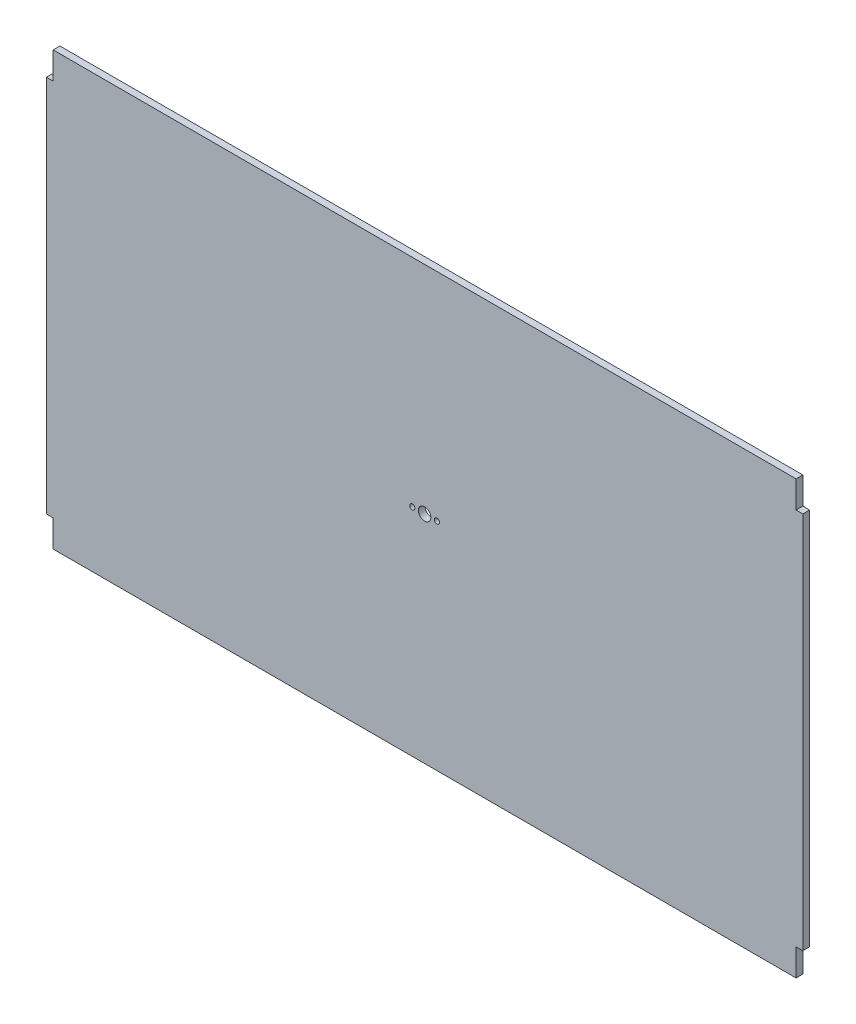
SolidWorks part; units mm, degrees
ref_plane "Front Plane" through (0, 0, 0) normal (0, 0, 1) x (1, 0, 0)
ref_plane "Top Plane" through (0, 0, 0) normal (0, 1, 0) x (1, 0, 0)
ref_plane "Right Plane" through (0, 0, 0) normal (1, 0, 0) x (0, 0, -1)
sketch "Sketch1" plane through (0, 0, 0) normal (0, 0, 1) x (1, 0, 0)
  line L0 (3.175, 203.2) -> (3.175, 190.5)
  line L1 (3.175, 0) -> (352.425, 0)
  line L2 (0, 12.7) -> (0, 190.5)
  line L3 (3.175, 203.2) -> (352.425, 203.2)
  line L4 (355.6, 12.7) -> (355.6, 190.5)
  line L5 (3.175, 190.5) -> (0, 190.5)
  line L6 (3.175, 12.7) -> (0, 12.7)
  line L7 (3.175, 12.7) -> (3.175, 0)
  line L8 (352.425, 0) -> (352.425, 12.7)
  line L9 (352.425, 12.7) -> (355.6, 12.7)
  line L10 (352.425, 203.2) -> (352.425, 190.5)
  line L11 (352.425, 190.5) -> (355.6, 190.5)
  dimension "D1" = 355.6
  dimension "D3" = 12.7
  dimension "D4" = 12.7
  dimension "D5" = 12.7
  dimension "D6" = 12.7
  dimension "D7" = 3.175
  dimension "D8" = 3.175
  dimension "D9" = 3.175
extrude "Boss-Extrude1" add sketch "Sketch1" along normal blind 3.175
sketch "Sketch2" plane through (0, 0, 3.175) normal (0, 0, 1) x (1, 0, 0)
  line L0 (355.6, 101.6) -> (-49644.4, 101.6) construction
  line L1 (355.6, 12.7) -> (355.6, 190.5) construction
  line L2 (0, 190.5) -> (0, 12.7) construction
  line L3 (177.8, -796.8) -> (177.8, 49203.2) construction
  line L4 (352.425, 203.2) -> (3.175, 203.2) construction
  circle A0 centre (177.8, 101.6) radius 2.921
  circle A1 centre (183.5785, 101.6) radius 1.2065
  circle A2 centre (172.0215, 101.6) radius 1.2065
  point P4 (355.6, 101.6)
  point P7 (0, 101.6)
  point P13 (177.8, 203.2)
  dimension "D1" = 5.842
  dimension "D2" = 2.413
  dimension "D3" = 5.7785
  dimension "D4" = 5.7785
extrude "Cut-Extrude1" cut sketch "Sketch2" against normal through all
